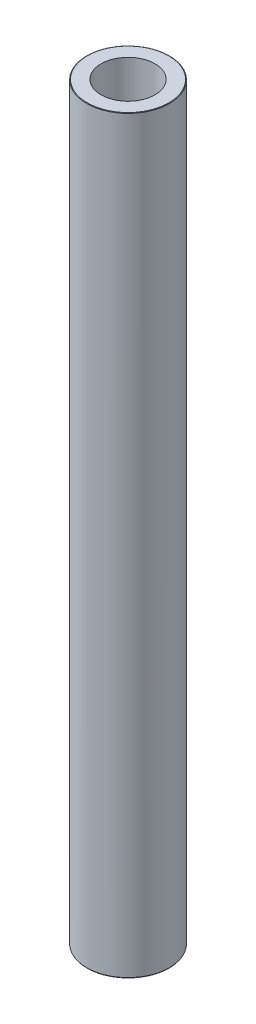
SolidWorks part; units mm, degrees
ref_plane "Front Plane" through (0, 0, 0) normal (0, 0, 1) x (1, 0, 0)
ref_plane "Top Plane" through (0, 0, 0) normal (0, 1, 0) x (1, 0, 0)
ref_plane "Right Plane" through (0, 0, 0) normal (1, 0, 0) x (0, 0, -1)
sketch "Sketch1" plane through (0, 0, 0) normal (0, 1, 0) x (1, 0, 0)
  circle A0 centre (0, 0) radius 25
  dimension "SHAFT_OD" = 50
extrude "Boss-Extrude1" add sketch "Sketch1" along normal blind 453.2408
sketch "Sketch2" plane through (0, 0, 0) normal (0, 1, 0) x (1, 0, 0)
  circle A0 centre (0, 0) radius 16.2934
  dimension "BORE_D" = 32.5868
extrude "Cut-Extrude1" cut sketch "Sketch2" along normal through all
chamfer "Chamfer1" distance 0.2113 angle 60 2 edges at (0, 453.2408, 25) (0, 0, 25) first distance on face at (0, 453.2408, 25) first distance on face at (0, 0, 16.2934)
